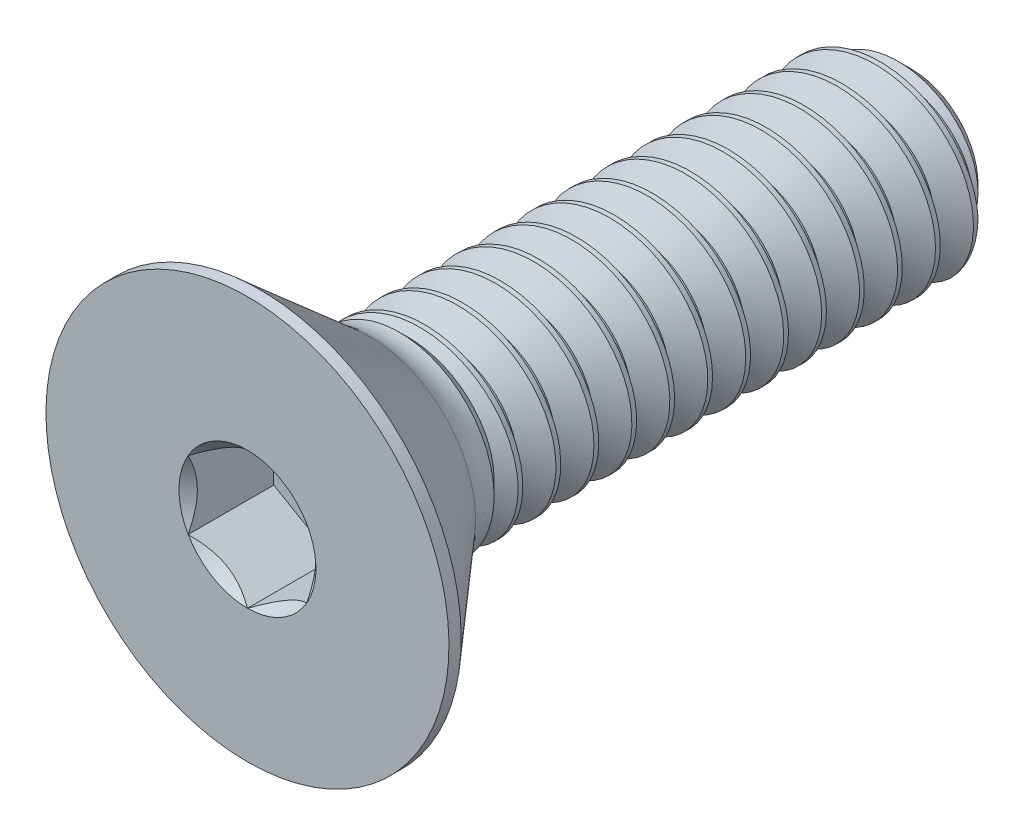
SolidWorks part; units mm, degrees
ref_plane "Front" through (0, 0, 0) normal (0, 0, 1) x (1, 0, 0)
ref_plane "Top" through (0, 0, 0) normal (0, 1, 0) x (1, 0, 0)
ref_plane "Right" through (0, 0, 0) normal (1, 0, 0) x (0, 0, -1)
sketch "Sketch1" plane through (0, 0, 0) normal (1, 0, 0) x (0, 0, -1)
  line L0 (0, 6.7437) -> (0.4089, 6.7437) construction
  line L1 (0.4089, 6.7437) -> (4.0894, 3.5443) construction
  line L2 (0, 3.175) -> (22.225, 3.175)
  line L3 (22.225, 3.175) -> (22.225, 0)
  line L4 (22.225, 0) -> (0, 0)
  line L5 (0, 0) -> (0, 6.7437) construction
  line L6 (0, 6.7437) -> (0, -6.7437) construction
  line L7 (22.225, 3.175) -> (22.225, -3.175) construction
  line L8 (0, -6.7437) -> (0.4089, -6.7437) construction
  line L9 (0.4089, -6.7437) -> (4.0894, -3.5443) construction
  line L11 (0, 3.175) -> (0, 0)
  line L12 (5.0772, 3.175) -> (5.0772, 0) construction
  arc A1 (4.0894, 3.5443) -> (5.0772, 3.175) centre (5.0772, 4.6807) ccw construction
  dimension "D1" = 0.4089
  dimension "Head Ht" = 4.0894
  dimension "Head Dia" = 13.4874
  dimension "Dia" = 6.35
  dimension "Lg" = 22.225
  dimension "Head Angle" = 82
revolve "Revolve1" add sketch "Sketch1" angle 360 about L4
sketch "Sketch3" plane through (0, 0, -22.225) normal (0, 0, -1) x (-1, 0, 0)
  circle A0 centre (0, 0) radius 3.175
curve "Helix/Spiral1" pitch 1.27 height 22.225 radius 3.175 centre (0, 0, -22.225) axis (0, 0, 1) start towards (0, 1, 0)
sketch "Sketch2" plane through (0, 0, 0) normal (1, 0, 0) x (0, 0, -1)
  line L0 (22.225, 3.175) -> (23.3362, 3.175)
  line L1 (23.3362, 3.175) -> (22.86, 2.3501)
  line L2 (22.86, 2.3501) -> (22.7012, 2.3501)
  line L3 (22.7012, 2.3501) -> (22.225, 3.175)
  line L4 (22.4631, 2.7626) -> (23.0981, 2.7626) construction
  dimension "D1" = 60
  dimension "D2" = 0.1588
  dimension "D3" = 0.635
chamfer "Chamfer1" distance 0.9525 angle 45 1 edges at (0, 3.175, -22.225)
sweep "Cut-Sweep1" cut profiles "Sketch2" path "Helix/Spiral1"
sketch "Sketch7" plane through (0, 0, 0) normal (1, 0, 0) x (0, 0, -1)
  line L0 (0, 6.7437) -> (0.4089, 6.7437) construction
  line L1 (0.4089, 6.7437) -> (4.0894, 3.5443) construction
  line L2 (0, 6.7437) -> (0.4089, 6.7437)
  line L3 (0.4089, 6.7437) -> (4.0894, 3.5443)
  line L4 (5.0772, 3.175) -> (5.0772, 0) construction
  line L5 (5.0772, 3.175) -> (5.0772, 0)
  line L7 (0, 0) -> (0, 6.7437) construction
  line L8 (0, 0) -> (0, 6.7437)
  line L9 (0, 0) -> (5.0772, 0)
  line L10 (7.4181, 0) -> (-7.4181, 0) construction
  arc A0 (4.0894, 3.5443) -> (5.0772, 3.175) centre (5.0772, 4.6807) ccw construction
  arc A1 (4.0894, 3.5443) -> (5.0772, 3.175) centre (5.0772, 4.6807) ccw
revolve "Revolve2" add sketch "Sketch7" angle 360 about L9
ref_plane "Plane1" through (0, 0, -5.0772) normal (0, 0, 1) x (1, 0, 0)
sketch "Sketch8" plane through (0, 0, -5.0772) normal (0, 0, 1) x (1, 0, 0)
  circle A0 centre (0, 0) radius 3.175
extrude "Boss-Extrude1" add sketch "Sketch8" against normal through all draft 45
sketch "Sketch11" [suppressed] plane through (0, 0, 0) normal (1, 0, 0) x (0, 0, -1)
  line L0 (4.4996, 0) -> (-4.4996, 0) construction
  line L1 (7.3025, 3.8989) -> (1.7272, 3.8989)
  line L2 (7.3025, 3.8989) -> (7.3025, -3.8989)
  line L3 (7.3025, -3.8989) -> (1.7272, -3.8989)
  line L4 (1.7272, 3.8989) -> (1.7272, -3.8989)
  line L5 (0, 3.8989) -> (0.1727, 3.8989) construction
  line L7 (4.7625, 1.7526) -> (4.7625, 0) construction
  point P4 (1.7272, 0)
  dimension "D1" = 2.54
extrude "Cut-Extrude4" [suppressed] cut sketch "Sketch11" against normal through all and the other way through all
combine bodies "Combine1" operation type add bodies to combine 117 114
sketch "Sketch5" plane through (0, 0, 0) normal (0, 0, 1) x (1, 0, 0)
  line L1 (1.9844, -1.1457) -> (1.9844, 1.1457)
  line L2 (1.9844, 1.1457) -> (0, 2.2914)
  line L3 (0, 2.2914) -> (-1.9844, 1.1457)
  line L4 (-1.9844, 1.1457) -> (-1.9844, -1.1457)
  line L5 (-1.9844, -1.1457) -> (0, -2.2914)
  line L6 (0, -2.2914) -> (1.9844, -1.1457)
  circle A0 centre (0, 0) radius 1.9844 construction
  dimension "Hex" = 3.9688
extrude "Cut-Extrude2" cut sketch "Sketch5" against normal blind 2.8626
sketch "Sketch6" plane through (0, 0, 0) normal (0, 0, 1) x (1, 0, 0)
  circle A0 centre (0, 0) radius 2.2914
extrude "Cut-Extrude3" cut sketch "Sketch6" against normal blind 2.8626 draft 45
sketch "Sketch9" [suppressed] plane through (0, 0, -5.0772) normal (0, 0, 1) x (1, 0, 0)
  circle A1 centre (0, 0) radius 3.175
  circle A2 centre (0, 0) radius 3.175
  point P0 (0, 3.175)
  dimension "D1" = 0
extrude "Boss-Extrude2" [suppressed] add sketch "Sketch9" against normal offset from surface (20.3228 mm away) 44.45 up to face at (0, 2.2225, -22.225)
sketch "Sketch10" plane through (0, 0, 0) normal (1, 0, 0) x (0, 0, -1)
  line L0 (22.225, 3.175) -> (22.225, -3.175) construction
  point P0 (20.32, -3.175)
  dimension "D1" = 1.905
equation "\"D3@Helix/Spiral1\" = \"Lg@Sketch1\""
equation "\"D2@Sketch2\" = \"D4@Helix/Spiral1\" * .125"
equation "\"D3@Sketch2\" = \"D4@Helix/Spiral1\" * .5"
equation "\"D1@Chamfer1\" = \"D4@Helix/Spiral1\" * .75"
equation "\"D1@Cut-Extrude2\" = \"Head Ht@Sketch1\" * .7"
equation "\"D1@Sketch1\" = \"Head Ht@Sketch1\" * .1"
equation "\"D1@Sketch10\" = \"D4@Helix/Spiral1\" * 1.5"
equation "\"D1@Cut-Extrude3\" = \"D1@Cut-Extrude2\""
